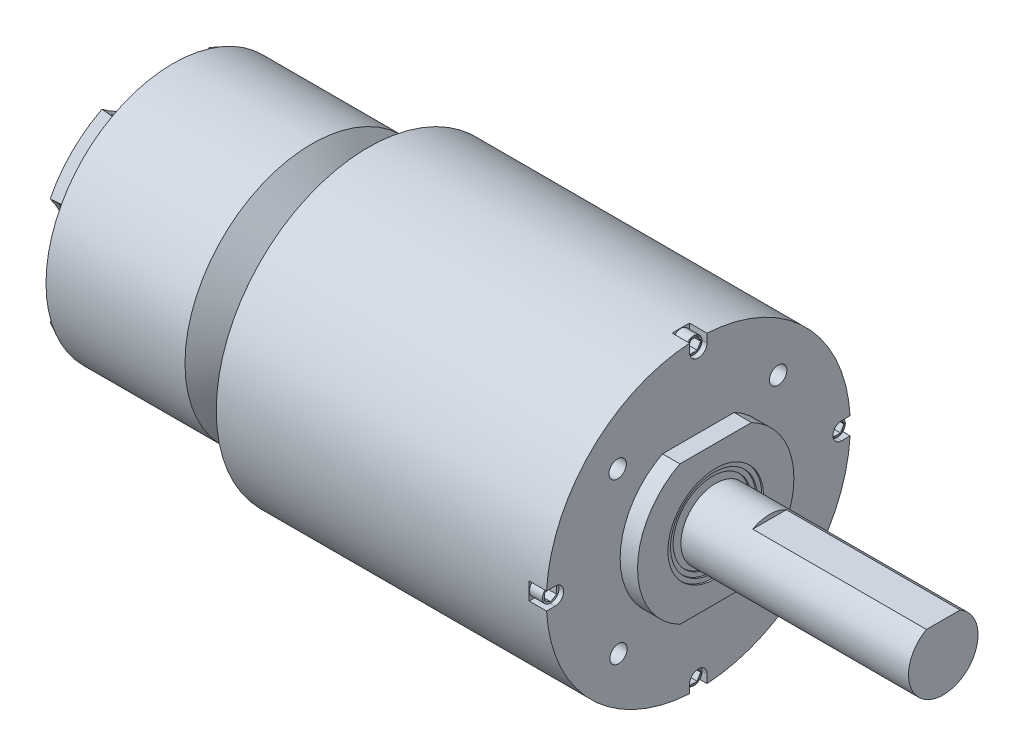
SolidWorks part; units mm, degrees
ref_plane "Front Plane" through (0, 0, 0) normal (0, 0, 1) x (1, 0, 0)
ref_plane "Top Plane" through (0, 0, 0) normal (0, 1, 0) x (1, 0, 0)
ref_plane "Right Plane" through (0, 0, 0) normal (1, 0, 0) x (0, 0, -1)
sketch "Sketch1" plane through (0, 0, 0) normal (0, 0, 1) x (1, 0, 0)
  line L0 (0, 0) -> (92.7, 0)
  line L1 (0, 0) -> (0, 1.6)
  line L2 (0, 1.6) -> (1, 1.6)
  line L3 (1, 1.6) -> (1, 5.6)
  line L4 (1, 5.6) -> (2, 5.6)
  line L5 (2, 5.6) -> (2, 13.6)
  line L6 (26, 0) -> (26.5, 0)
  line L7 (26.5, 0) -> (26.5, 17.5)
  line L8 (4, 14.6) -> (20, 14.6)
  line L10 (26, 4) -> (24, 4)
  line L11 (24, 4) -> (24, 9.6)
  line L12 (26.5, 17.5) -> (64.5, 17.5)
  line L13 (64.5, 17.5) -> (64.5, 5.6)
  line L14 (20, 14.6) -> (24, 9.6)
  line L15 (2, 13.6) -> (4, 14.6)
  line L16 (64.5, 5.6) -> (66.5, 5.6)
  line L17 (66.5, 5.6) -> (66.5, 5)
  line L20 (66.7, 4) -> (92.7, 4)
  line L21 (92.7, 4) -> (92.7, 0)
  line L22 (26.5, 0) -> (27.5, 0)
  line L23 (27.5, 0) -> (28, 0)
  line L24 (28, 0) -> (28, 16)
  line L25 (28, 16) -> (63, 16)
  line L26 (63, 16) -> (63, 0)
  line L27 (3, 13.6) -> (3, 0)
  line L28 (3, 13.6) -> (20, 13.6)
  line L29 (20, 13.6) -> (23.1769, 9.6)
  line L30 (23.1769, 9.6) -> (23.1769, 0)
  line L31 (26.5, 0) -> (26.5, 1.6)
  line L32 (26.5, 1.6) -> (26, 1.6)
  line L33 (26, 1.6) -> (26, 4)
  line L34 (66.5, 5) -> (66.5, 4)
  line L35 (66.5, 4) -> (66.7, 4)
revolve "Revolve2" add sketch "Sketch1" angle 360 about L0
sketch "Sketch5" plane through (64.5, 0, 0) normal (1, 0, 0) x (0, 0, -1)
  line L0 (0, 0) -> (0, 8)
  line L3 (0, 0) -> (0, -8)
  line L5 (-4.1231, -8) -> (4.1231, -8)
  line L6 (-4.1231, 8) -> (4.1231, 8)
  arc A1 (4.1231, -8) -> (4.1231, 8) centre (0, 0) ccw
  arc A2 (-4.1231, -8) -> (-4.1231, 8) centre (0, 0) cw
  circle M6 centre (0, 0) radius 5.6
extrude "Boss-Extrude1" add sketch "Sketch5" along normal blind 2 contours L5 A1 L6 L0 L3 M6 | A2 L5 L3 L0 L6 M6
sketch "Sketch6" plane through (66.5, 0, 0) normal (1, 0, 0) x (0, 0, -1)
  circle A0 centre (0, 0) radius 4.5
extrude "Cut-Extrude7" cut sketch "Sketch6" against normal blind 0.6
sketch "Sketch8" plane through (66.5, 0, 0) normal (1, 0, 0) x (0, 0, -1)
  circle A0 centre (0, 0) radius 5
extrude "Cut-Extrude8" cut sketch "Sketch8" against normal blind 0.4
sketch "Sketch9" plane through (66.5, 0, 0) normal (1, 0, 0) x (0, 0, -1)
  circle A0 centre (0, 0) radius 5.5
extrude "Cut-Extrude9" cut sketch "Sketch9" against normal blind 0.2
sketch "Sketch10" plane through (92.7, 0, 0) normal (1, 0, 0) x (0, 0, -1)
  line L0 (0, 0) -> (0, 3.5)
  line L2 (1.9365, 3.5) -> (-1.9365, 3.5)
  circle A0 centre (0, 0) radius 4 construction
  arc A1 (-1.9365, 3.5) -> (1.9365, 3.5) centre (0, 0) cw
extrude "Cut-Extrude11" cut sketch "Sketch10" against normal blind 20 contours L2 A1
sketch "Sketch11" plane through (64.5, 0, 0) normal (1, 0, 0) x (0, 0, -1)
  line L0 (0, 0) -> (9.1924, 9.1924)
  circle A0 centre (0, 0) radius 13
  circle A2 centre (9.1924, 9.1924) radius 1
extrude "Cut-Extrude13" cut sketch "Sketch11" against normal blind 4 contours A2
pattern_circular "CirPattern2" count 4 over 360 about axis through (0, -0.0989, 0) along (1, 0, 0) of "Cut-Extrude13"
sketch "Sketch12" plane through (64.5, 0, 0) normal (1, 0, 0) x (0, 0, -1)
  line L0 (-1, 16.5) -> (-1, 17.4714)
  line L2 (1, 16.5) -> (1, 17.4714)
  circle A0 centre (0, 0) radius 16.5
  arc A1 (-1, 16.5) -> (1, 16.5) centre (0, 16.5) ccw
  circle A2 centre (0, 0) radius 17.5 construction
  arc A3 (-1, 17.4714) -> (1.0356, 17.4693) centre (0, 0) cw
  circle M10 centre (0, 0) radius 17.5
extrude "Cut-Extrude20" cut sketch "Sketch12" against normal blind 4 contours A0 A1 | L0 A1 A0 L2 M10
sketch "Sketch13" plane through (60.5, 0, 0) normal (1, 0, 0) x (0, 0, -1)
  circle A0 centre (0, 16.5) radius 0.95
extrude "Boss-Extrude2" add sketch "Sketch13" along normal blind 3.5
sketch "Sketch14" plane through (64, 0, 0) normal (1, 0, 0) x (0, 0, -1)
  line L5 (-0.4, 17.1928) -> (0.4, 17.1928)
  line L6 (0.4, 17.1928) -> (0.8, 16.5)
  line L7 (0.8, 16.5) -> (0.4, 15.8072)
  line L8 (0.4, 15.8072) -> (-0.4, 15.8072)
  line L10 (-0.4, 15.8072) -> (-0.8, 16.5)
  line L11 (-0.8, 16.5) -> (-0.4, 17.1928)
extrude "Cut-Extrude21" cut sketch "Sketch14" against normal blind 1
fillet "Fillet2" radius 0.05 7 edges at (64, 16.5, -0.95) (64, 16.1536, 0.6) (64, 15.8072, 0) (64, 16.1536, -0.6) (64, 16.8464, -0.6) (64, 17.1928, 0) (64, 16.8464, 0.6)
sketch "Sketch15" plane through (60.5, 0, 0) normal (1, 0, 0) x (0, 0, -1)
  line L0 (-1, 16.5) -> (-1, 17.4714)
  line L1 (1, 16.5) -> (1, 17.4714)
  arc A0 (-1, 17.4714) -> (1, 17.4714) centre (0, 0) ccw
  arc A1 (1, 17.4714) -> (-1, 17.4714) centre (0, 0) ccw construction
  arc A2 (-1, 16.5) -> (1, 16.5) centre (0, 16.5) ccw
  arc A3 (-1, 16.5) -> (1, 16.5) centre (0, 16.5) ccw construction
  arc A4 (-1, 17.4714) -> (1, 17.4714) centre (0, 0) cw
extrude "Boss-Extrude7" add sketch "Sketch15" along normal blind 2
sketch "Sketch16" plane through (64.5, 0, 0) normal (1, 0, 0) x (0, 0, -1)
  line L0 (-16.5, 1) -> (-17.4714, 1)
  line L2 (-16.5, -1) -> (-17.4714, -1)
  line L3 (-1, -16.5) -> (-1, -17.4714)
  line L5 (1, -16.5) -> (1, -17.4714)
  line L6 (16.5, 1) -> (17.4714, 1)
  line L7 (16.5, -1) -> (17.4714, -1)
  circle A0 centre (0, 0) radius 16.5
  arc A1 (16.5, 1) -> (16.5, -1) centre (16.5, 0) ccw
  arc A2 (1, -16.5) -> (-1, -16.5) centre (0, -16.5) ccw
  arc A3 (-16.5, -1) -> (-16.5, 1) centre (-16.5, 0) ccw
  arc A4 (-1, 17.4714) -> (1, 17.4714) centre (0, 0) ccw construction
  arc A5 (-17.4714, -1) -> (-17.4714, 1) centre (0, 0) cw
  arc A6 (17.4714, 1) -> (17.4714, -1) centre (0, 0) cw
  arc A7 (1, -17.4714) -> (-1.0415, -17.469) centre (0, 0) cw
  arc M12 (-1, 17.4714) -> (1, 17.4714) centre (0, 0) ccw
extrude "Cut-Extrude23" cut sketch "Sketch16" against normal blind 2 contours L5 A2 A0 L3 M12 | A0 A2 | L6 A1 A0 L7 M12 | A0 A1 | A0 A3 L0 L2 M12 | A0 A3
sketch "Sketch17" plane through (62.5, 0, 0) normal (1, 0, 0) x (0, 0, -1)
  circle A0 centre (16.5, 0) radius 0.95
  circle A1 centre (0, -16.5) radius 0.95
  circle A2 centre (-16.5, 0) radius 0.95
extrude "Boss-Extrude8" add sketch "Sketch17" along normal blind 1.5
sketch "Sketch18" plane through (64, 0, 0) normal (1, 0, 0) x (0, 0, -1)
  line L5 (-17.1928, 0.4) -> (-16.5, 0.8)
  line L6 (-16.5, 0.8) -> (-15.8072, 0.4)
  line L7 (-15.8072, -0.4) -> (-15.8072, 0.4)
  line L8 (-15.8072, -0.4) -> (-16.5, -0.8)
  line L9 (-17.1928, -0.4) -> (-16.5, -0.8)
  line L10 (-17.1928, -0.4) -> (-17.1928, 0.4)
  circle A2 centre (16.5, 0) radius 0.8
  circle A3 centre (0, -16.5) radius 0.8
extrude "Cut-Extrude24" cut sketch "Sketch18" against normal blind 1
sketch "Sketch20" plane through (63, 0, 0) normal (1, 0, 0) x (0, 0, -1)
  circle A0 centre (0, -16.5) radius 0.8
  circle A1 centre (16.5, 0) radius 0.8
extrude "Boss-Extrude9" add sketch "Sketch20" along normal blind 1
sketch "Sketch21" plane through (64, 0, 0) normal (1, 0, 0) x (0, 0, -1)
  line L0 (16.9, 0.6928) -> (17.3, 0)
  line L4 (15.7, 0) -> (16.1, -0.6928)
  line L7 (0.4, -17.1928) -> (-0.4, -17.1928)
  line L9 (-0.4, -15.8072) -> (0.4, -15.8072)
  line L10 (0.4, -15.8072) -> (0.8, -16.5)
  line L11 (0.4, -17.1928) -> (0.8, -16.5)
  line L12 (-0.4, -17.1928) -> (-0.8, -16.5)
  line L13 (-0.8, -16.5) -> (-0.4, -15.8072)
  line L15 (16.9, -0.6928) -> (16.1, -0.6928)
  line L16 (16.9, -0.6928) -> (17.3, 0)
  line L18 (16.9, 0.6928) -> (16.1, 0.6928)
  line L19 (16.1, 0.6928) -> (15.7, 0)
extrude "Cut-Extrude27" cut sketch "Sketch21" against normal blind 1
fillet "Fillet3" radius 0.05 14 edges at (64, -16.5, -0.95) (64, -16.8464, 0.6) (64, -17.1928, 0) (64, -16.8464, -0.6) (64, -16.1536, -0.6) (64, -15.8072, 0) (64, -16.1536, 0.6) (64, 0, -17.45) (64, 0.3464, -17.1) (64, 0.6928, -16.5) (64, 0.3464, -15.9) (64, -0.3464, -15.9) (64, -0.6928, -16.5) (64, -0.3464, -17.1)
sketch "Sketch22" plane through (2, 0, 0) normal (-1, 0, 0) x (0, 0, 1)
  circle A0 centre (0, 0) radius 20
  circle A1 centre (20, 0) radius 10
  circle A2 centre (0, -20) radius 10
  circle A3 centre (-20, 0) radius 10
  circle A4 centre (0, 20) radius 10
  circle M2 centre (0, 0) radius 13.6
extrude "Cut-Extrude28" cut sketch "Sketch22" against normal blind 2 contours A0 A4 | A0 A4 M2 | A4 M2 | A0 A1 | A0 A1 M2 | A1 M2 | A0 A3 | A3 A0 M2 | A3 M2 | A2 M2 | A0 A2 M2 | A0 A2
sketch "Sketch23" plane through (2, 0, 0) normal (-1, 0, 0) x (0, 0, 1)
  line L0 (0, 0) -> (6.7175, 6.7175)
  line L1 (6.7175, 6.7175) -> (-6.7175, -6.7175)
  line L2 (0, 0) -> (-5.6569, 5.6569)
  line L3 (0, 0) -> (5.6569, -5.6569)
  circle A0 centre (0, 0) radius 8
  circle A1 centre (0, 0) radius 9.5
  circle A2 centre (-5.6569, 5.6569) radius 1
  circle A3 centre (6.7175, 6.7175) radius 1
  circle A4 centre (5.6569, -5.6569) radius 1
  circle A5 centre (-6.7175, -6.7175) radius 1
extrude "Cut-Extrude29" cut sketch "Sketch23" against normal blind 2 contours A2 | A3 | A4 | A5
